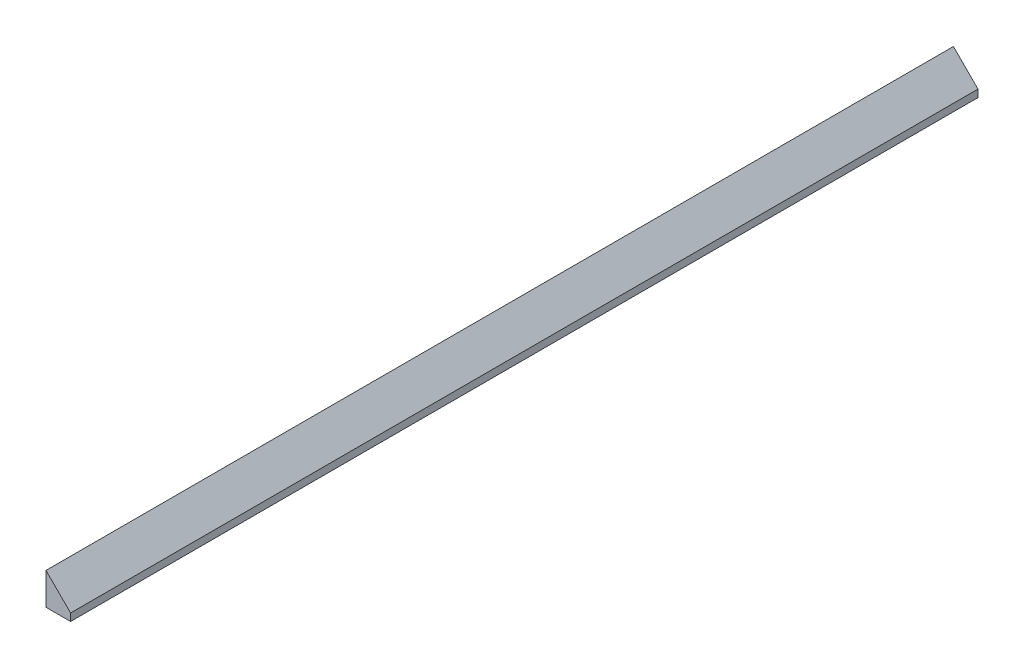
SolidWorks part; units mm, degrees
material "6061-T6 (SS)"
ref_plane "Front Plane" through (0, 0, 0) normal (0, 0, 1) x (1, 0, 0)
ref_plane "Top Plane" through (0, 0, 0) normal (0, 1, 0) x (1, 0, 0)
ref_plane "Right Plane" through (0, 0, 0) normal (1, 0, 0) x (0, 0, -1)
sketch "Sketch1" plane through (0, 0, 0) normal (0, 0, 1) x (1, 0, 0)
  line L5 (0, 0) -> (2.6, 0)
  line L6 (2.6, 0) -> (0, 2.6)
  line L7 (0, 2.6) -> (0, 0)
  line L11 (2, 0) -> (2, 0.6)
  dimension "D1" = 0.6
  dimension "D2" = 2.6
extrude "Boss-Extrude1" add sketch "Sketch1" against normal mid plane 73.8 contours L5 L11 L6 L7 region at (0.7917, 0.9042, 0)
